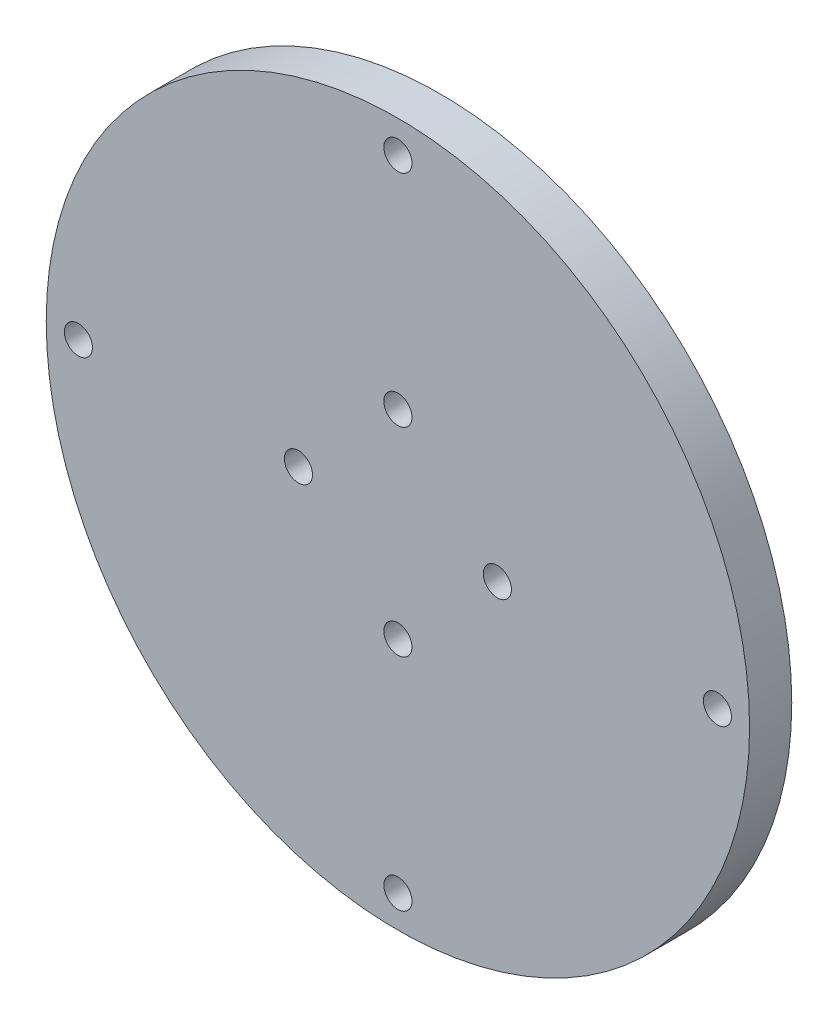
SolidWorks part; units mm, degrees
material "1060 Alloy"
ref_plane "Front Plane" through (0, 0, 0) normal (0, 0, 1) x (1, 0, 0)
ref_plane "Top Plane" through (0, 0, 0) normal (0, 1, 0) x (1, 0, 0)
ref_plane "Right Plane" through (0, 0, 0) normal (1, 0, 0) x (0, 0, -1)
sketch "Sketch1" plane through (0, 0, 0) normal (0, 0, 1) x (1, 0, 0)
  line L0 (-25, 0) -> (25, 0) construction
  line L5 (0, 25) -> (0, -25) construction
  line L6 (-7.0711, 0) -> (0, 7.0711) construction
  line L7 (0, 7.0711) -> (7.0711, 0) construction
  line L8 (7.0711, 0) -> (0, -7.0711) construction
  line L9 (0, -7.0711) -> (-7.0711, 0) construction
  circle A0 centre (0, 0) radius 25
  circle A9 centre (0, 0) radius 22.715
  circle A10 centre (0, 22.715) radius 1
  circle A11 centre (0, 7.0711) radius 1
  circle A12 centre (7.0711, 0) radius 1
  circle A13 centre (0, -7.0711) radius 1
  circle A14 centre (-7.0711, 0) radius 1
  circle A16 centre (22.715, 0) radius 1
  circle A17 centre (0, -22.715) radius 1
  circle A18 centre (-22.715, 0) radius 1
  point P5 (0, 25)
  point P16 (0, -25)
  dimension "D1" = 50
  dimension "D2" = 45.43
  dimension "D8" = 10
  dimension "D9" = 2
  dimension "D10" = 2
  dimension "D11" = 2
  dimension "D12" = 2
  dimension "D3" = 2
  dimension "D4" = 2
  dimension "D5" = 2
  dimension "D13" = 2
  dimension "D6" = 90
  dimension "D7" = 90
extrude "Boss-Extrude1" add sketch "Sketch1" along normal mid plane 3 contours A0 A12 A13 A18 A17 A16 A10 | A13 A12 | A0 A9 A16 A17 A18 A10 region at (-24.2929, 0, 0) region at (0, 0, 0)
